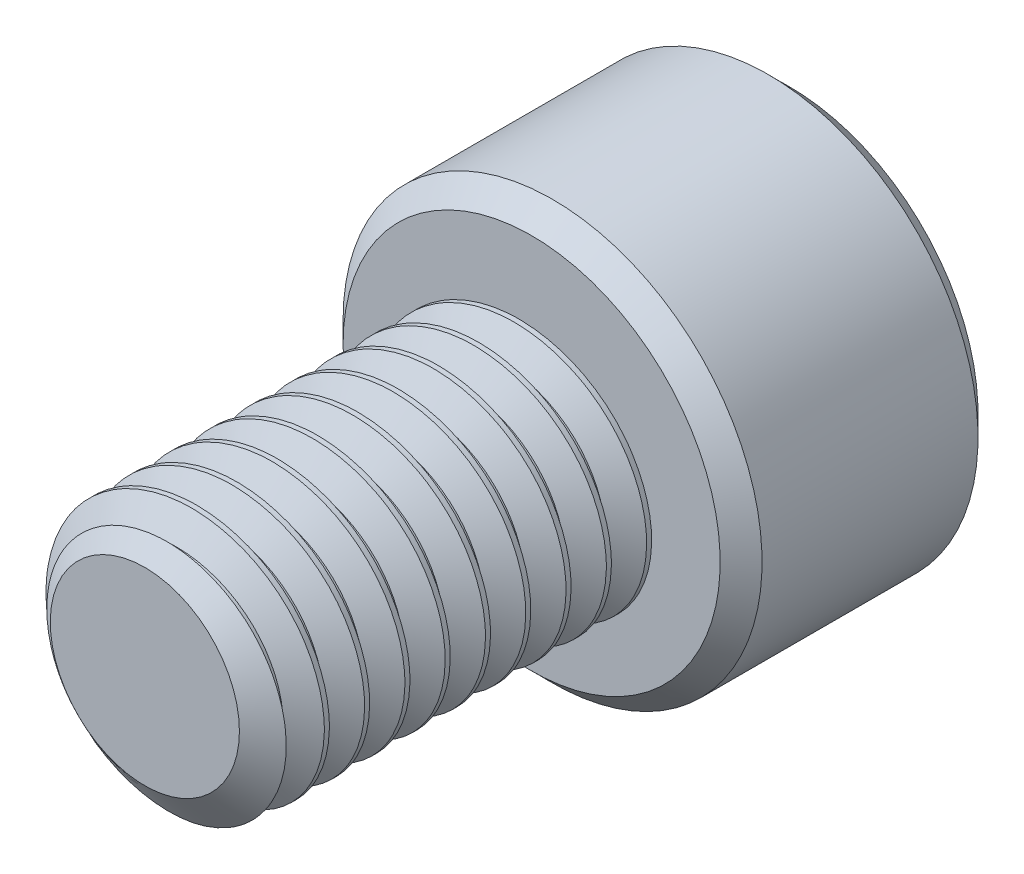
SolidWorks part; units mm, degrees
ref_plane "Front Plane" through (0, 0, 0) normal (0, 0, 1) x (1, 0, 0)
ref_plane "Top Plane" through (0, 0, 0) normal (0, 1, 0) x (1, 0, 0)
ref_plane "Right Plane" through (0, 0, 0) normal (1, 0, 0) x (0, 0, -1)
sketch "Sketch1" plane through (0, 0, 0) normal (0, 0, 1) x (1, 0, 0)
  circle A0 centre (0, 0) radius 4
  dimension "OD" = 8
extrude "Extrude1" add sketch "Sketch1" against normal blind 12
sketch "Sketch2" plane through (0, 0, 0) normal (0, 0, 1) x (1, 0, 0)
  circle A0 centre (0, 0) radius 4 construction
  circle A1 centre (0, 0) radius 4
curve "Helix/Spiral1" pitch 1.25 height 13.25 turns 10.6 parameters "pitch"=1.25
sketch "Sketch3" plane through (0, 0, 0) normal (1, 0, 0) x (0, 0, -1)
  line L0 (-1.0937, 4) -> (-0.625, 3.1881)
  line L1 (-0.625, 3.1881) -> (-0.4688, 3.1881)
  line L2 (-0.4688, 3.1881) -> (0, 4)
  line L3 (-1.0937, 4) -> (0, 4)
  line L4 (-0.5469, 4) -> (-0.5469, 3.1881) construction
  line L5 (-0.8594, 3.5941) -> (-0.2344, 3.5941) construction
  line L6 (0, 4) -> (0, -4) construction
  dimension "D1" = 0.1562
  dimension "D2" = 0.625
  dimension "D3" = 60
sweep "Cut-Sweep1" cut profiles "Sketch3" path "Helix/Spiral1"
sketch "Sketch4" plane through (0, 0, 0) normal (1, 0, 0) x (0, 0, -1)
  line L0 (0.7464, 4) -> (0, 2.9341)
  line L1 (0, 2.9341) -> (0, 4)
  line L2 (0.7464, 4) -> (0, 4)
  line L3 (-1.0937, 4) -> (0, 4) construction
  line L4 (0, 0) -> (7.0209, 0) construction
  dimension "D1" = 55
  dimension "D2" = 0.254
revolve "Cut-Revolve1" cut sketch "Sketch4" angle 360 about L4
sketch "Sketch5" plane through (0, 0, 0) normal (1, 0, 0) x (0, 0, -1)
  line L0 (12, -3.945) -> (12, 2.5877) construction
  line L1 (12, 4.127) -> (87.4327, 4.127)
  line L2 (12, 4.127) -> (12, 0)
  line L3 (12, 0) -> (87.3125, 0)
  line L4 (87.3125, 3.7968) -> (87.3125, 0)
  line L5 (87.4327, 4.127) -> (87.3125, 3.7968)
  line L6 (0, 0) -> (9.9695, 0) construction
  point P3 (87.3125, 4.127)
  point P10 (87.3125, 4.127)
  dimension "D1" = 0.3302
  dimension "Thread min" = 87.3125
  dimension "D2" = 0.127
  dimension "D3" = 20
revolve "partially thread" [suppressed] add sketch "Sketch5" angle 360 about L6
sketch "Sketch6" plane through (0, 0, -12) normal (0, 0, -1) x (-1, 0, 0)
  circle A0 centre (0, 0) radius 6.5
  dimension "head dia" = 13
extrude "Extrude2" add sketch "Sketch6" along normal blind 8
sketch "Sketch7" plane through (0, 0, -20) normal (0, 0, -1) x (-1, 0, 0)
  line L1 (0, 3.4641) -> (-3, 1.7321)
  line L2 (-3, 1.7321) -> (-3, -1.7321)
  line L3 (-3, -1.7321) -> (0, -3.4641)
  line L4 (0, -3.4641) -> (3, -1.7321)
  line L5 (3, -1.7321) -> (3, 1.7321)
  line L6 (3, 1.7321) -> (0, 3.4641)
  circle A0 centre (0, 0) radius 3 construction
  dimension "hex dia" = 6
extrude "Cut-Extrude1" cut sketch "Sketch7" against normal blind 4.5
sketch "Sketch8" plane through (0, 0, -20) normal (0, 0, -1) x (-1, 0, 0)
  circle A0 centre (0, 0) radius 3.4641
extrude "Cut-Extrude2" cut sketch "Sketch8" against normal through all draft 45
chamfer "Chamfer1" distance 0.65 angle 45 2 edges at (-6.5, 0, -20) (-6.5, 0, -12)
sketch "Sketch9" plane through (0, 0, 0) normal (1, 0, 0) x (0, 0, -1)
  line L0 (0, 4) -> (0, -4) construction
  line L1 (6.875, 4) -> (6.875, -4) construction
  dimension "D1" = 6.875
equation "\"D3@Helix/Spiral1\" = \"screw length@Extrude1\"+\"pitch@Helix/Spiral1\""
equation "\"D1@Sketch3\" = \"pitch@Helix/Spiral1\"*.125"
equation "\"D2@Sketch3\" = \"pitch@Helix/Spiral1\"*.5"
equation "\"D1@Cut-Extrude1\" = \"hex dia@Sketch7\"*.75"
equation "\"D1@Chamfer1\" = \"head dia@Sketch6\"*.05"
equation "\"D1@Sketch9\" = \"pitch@Helix/Spiral1\"*5.5"
